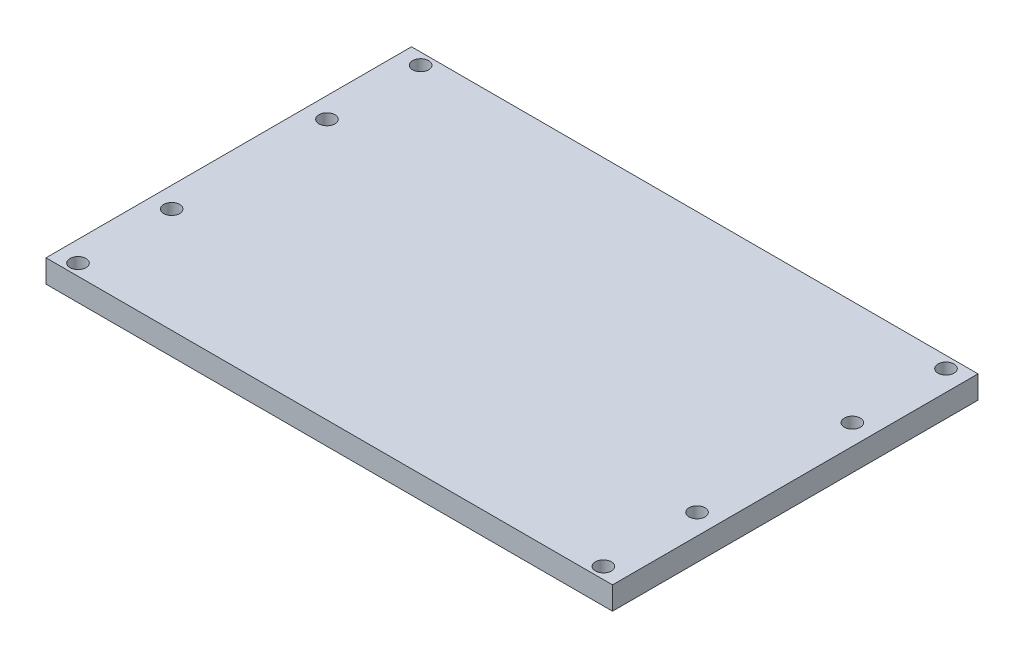
SolidWorks part; units mm, degrees
ref_plane "前视基准面" through (0, 0, 0) normal (0, 0, 1) x (1, 0, 0)
ref_plane "上视基准面" through (0, 0, 0) normal (0, 1, 0) x (1, 0, 0)
ref_plane "右视基准面" through (0, 0, 0) normal (1, 0, 0) x (0, 0, -1)
other "Configuration Table"
sketch "草图1" plane through (0, 0, 0) normal (0, 1, 0) x (1, 0, 0)
  line L5 (-62, -40) -> (62, -40)
  line L6 (-62, -40) -> (-62, 40)
  line L7 (-62, 40) -> (62, 40)
  line L8 (62, -40) -> (62, 40)
  line L9 (-62, -40) -> (62, 40) construction
  line L10 (-62, 40) -> (62, -40) construction
  point P0 (0, 0)
  dimension "D1" = 124
  dimension "D2" = 80
extrude "凸台-拉伸1" add sketch "草图1" along normal blind 5
sketch "草图2" plane through (0, 5, 0) normal (0, 1, 0) x (1, 0, 0)
  line L0 (-62, 40) -> (-62, -40) construction
  line L1 (62, 40) -> (-62, 40) construction
  line L2 (-62, -40) -> (62, -40) construction
  line L3 (-57.5, 37.5) -> (-57.5, -37.5)
  line L4 (57.5, 37.5) -> (57.5, -37.5)
  line L5 (62, -40) -> (62, 40) construction
  circle A0 centre (-57.5, 37.5) radius 1.15
  circle A1 centre (-57.5, 17) radius 1.15
  circle A2 centre (-57.5, -17) radius 1.15
  circle A3 centre (-57.5, -37.5) radius 1.15
  circle A4 centre (57.5, 37.5) radius 1.15
  circle A5 centre (57.5, 17) radius 1.15
  circle A6 centre (57.5, -17) radius 1.15
  circle A7 centre (57.5, -37.5) radius 1.15
  circle A8 centre (-57.5, 37.5) radius 1.75
  circle A9 centre (-57.5, 17) radius 1.75
  circle A10 centre (-57.5, -17) radius 1.75
  circle A11 centre (-57.5, -37.5) radius 1.75
  circle A12 centre (57.5, 37.5) radius 1.75
  circle A13 centre (57.5, 17) radius 1.75
  circle A14 centre (57.5, -17) radius 1.75
  circle A15 centre (57.5, -37.5) radius 1.75
  point P30 (45.813, -17)
  point P31 (45.813, 19.8305)
  point P32 (45.813, -2.5774)
  point P33 (45.813, 12.6328)
  point P34 (0, 0)
  point P37 (0, 0)
  point P38 (0, 0)
  point P39 (0, 0)
  point P40 (0, 0)
  point P41 (0, 0)
  point P42 (0, 0)
  point P43 (0, 0)
  dimension "D1" = 2.3
  dimension "D2" = 3.5
  dimension "D3" = 4.5
  dimension "D4" = 2.5
  dimension "D5" = 23
  dimension "D6" = 2.5
  dimension "D7" = 23
  dimension "D8" = 4.5
extrude "切除-拉伸1" cut sketch "草图2" against normal through all contours A1 | A2 | A3 | A0 | A4 | A5 | A6 | A7
extrude "切除-拉伸2" cut sketch "草图2<3>" against normal blind 3 contours A8 | A9 | A10 | A11 | A15 | A14 | A13 | A12
sketch "草图2<3>" plane through (0, 5, 0) normal (0, 1, 0) x (1, 0, 0) same geometry as "草图2"
